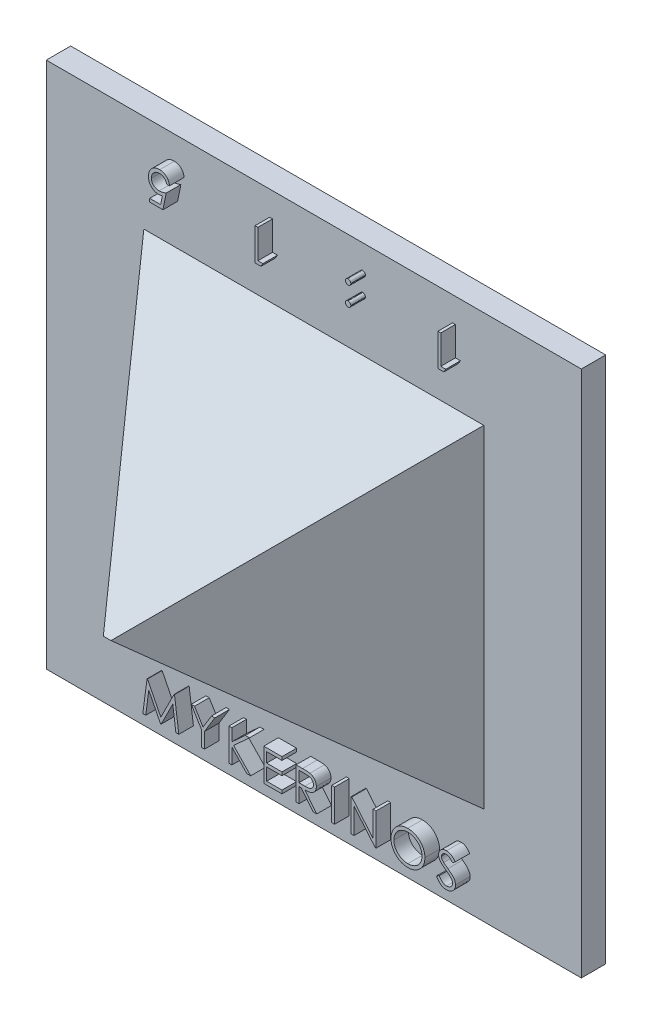
SolidWorks part; units mm, degrees
ref_plane "Plan de face" through (0, 0, 0) normal (0, 0, 1) x (1, 0, 0)
ref_plane "Plan de dessus" through (0, 0, 0) normal (0, 1, 0) x (1, 0, 0)
ref_plane "Plan de droite" through (0, 0, 0) normal (1, 0, 0) x (0, 0, -1)
sketch "Esquisse1" plane through (0, 0, 0) normal (0, 0, 1) x (1, 0, 0)
  line L1 (0, 0) -> (69.7, 0)
  line L2 (0, 0) -> (0, 68.13)
  line L3 (0, 68.13) -> (69.7, 68.13)
  line L4 (69.7, 0) -> (69.7, 68.13)
  dimension "D1" = 69.7
  dimension "D2" = 68.13
extrude "Boss.-Extru.1" add sketch "Esquisse1" along normal blind 50 draft 38.8
sketch "Esquisse3" plane through (0, 0, 0) normal (0, 0, -1) x (-1, 0, 0)
  line L8 (20, -20) -> (20, 88.13)
  line L9 (20, 88.13) -> (-89.7, 88.13)
  line L10 (-89.7, 88.13) -> (-89.7, -20)
  line L11 (-89.7, -20) -> (20, -20)
  line L12 (20, -20) -> (20, 88.13)
  line L13 (20, 88.13) -> (-89.7, 88.13)
  line L14 (-89.7, 88.13) -> (-89.7, -20)
  line L15 (-89.7, -20) -> (20, -20)
  dimension "D1" = 20
extrude "Boss.-Extru.3" add sketch "Esquisse3" along normal blind 5 separate body
sketch "Esquisse2" plane through (0, 0, -5) normal (0, 0, -1) x (-1, 0, 0)
  line L0 (0, 0) -> (-69.7, 0) construction
  line L1 (0, 68.13) -> (0, 0) construction
  circle A0 centre (-34.85, 34.065) radius 23.25
  point P5 (-34.85, 0)
  point P8 (0, 34.065)
  dimension "D1" = 46.5
extrude "Boss.-Extru.2" add sketch "Esquisse2" along normal blind 30
sketch "Esquisse4" plane through (0, 0, 0) normal (0, 0, 1) x (1, 0, 0)
  line L0 (2.2826, -15) -> (67.4174, -15) construction
  line L1 (3.5262, 83.13) -> (66.1738, 83.13) construction
  line L2 (0, 0) -> (69.7, 0) construction
  line L3 (89.7, -20) -> (-20, -20) construction
  line L4 (69.7, 68.13) -> (0, 68.13) construction
  line L5 (-20, 88.13) -> (89.7, 88.13) construction
  text T0 "MYKERINOS" font "Century Gothic" height in points 25
  text T1 "1:15" font "Century Gothic" height in points 25
  point P6 (34.85, 0)
  point P7 (34.85, -15)
  point P12 (34.85, 68.13)
  point P13 (34.85, 83.13)
  dimension "D1" = 5
  dimension "D2" = 5
extrude "Boss.-Extru.4" add sketch "Esquisse4" along normal blind 3
